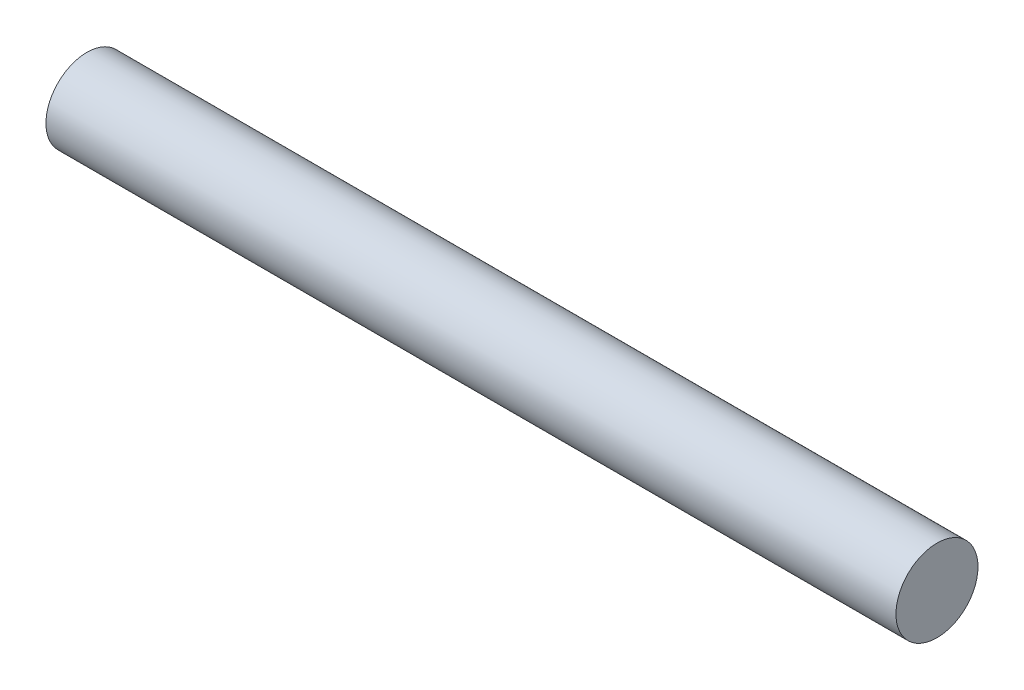
SolidWorks part; units mm, degrees
ref_plane "Front Plane" through (0, 0, 0) normal (0, 0, 1) x (1, 0, 0)
ref_plane "Top Plane" through (0, 0, 0) normal (0, 1, 0) x (1, 0, 0)
ref_plane "Right Plane" through (0, 0, 0) normal (1, 0, 0) x (0, 0, -1)
sketch "Sketch1" plane through (0, 0, 0) normal (1, 0, 0) x (0, 0, -1)
  circle A0 centre (0, 0) radius 2.413
extrude "Boss-Extrude1" add sketch "Sketch1" along normal blind 50
